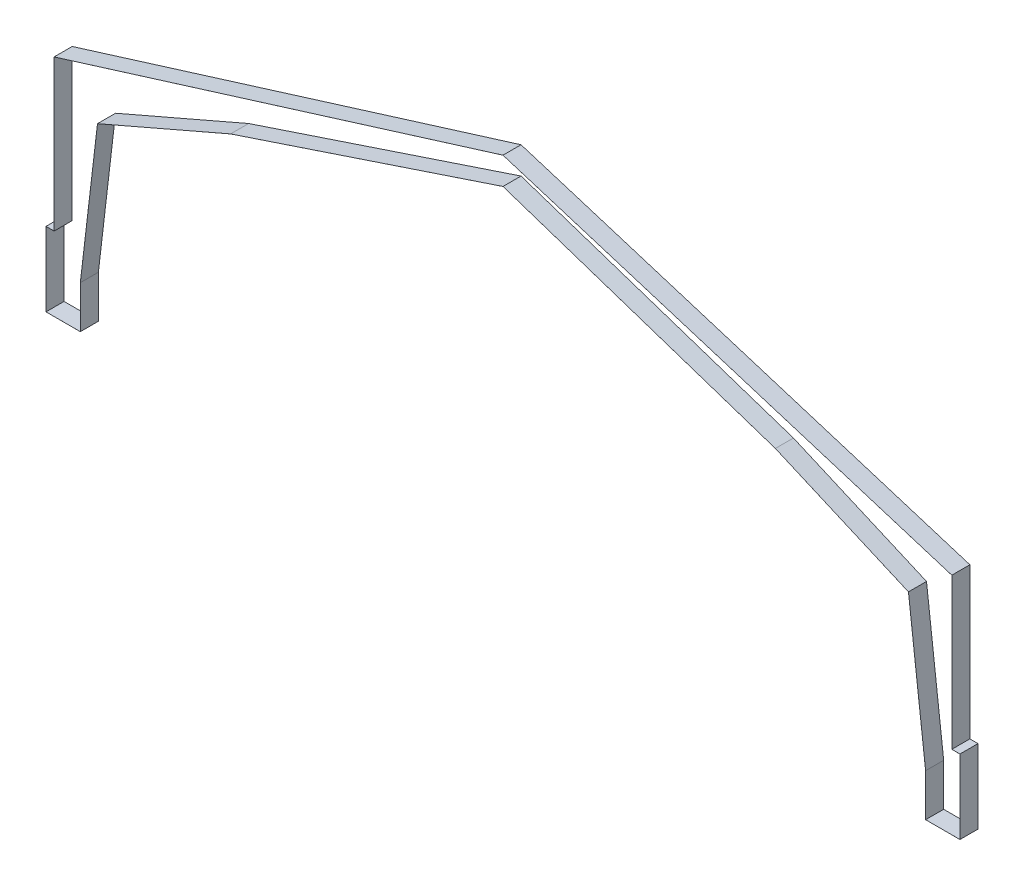
SolidWorks part; units mm, degrees
ref_plane "Alzado" through (0, 0, 0) normal (0, 0, 1) x (1, 0, 0)
ref_plane "Planta" through (0, 0, 0) normal (0, 1, 0) x (1, 0, 0)
ref_plane "Vista lateral" through (0, 0, 0) normal (1, 0, 0) x (0, 0, -1)
sketch "Croquis1" plane through (0, 0, 0) normal (0, 0, 1) x (1, 0, 0)
  line L0 (1447.8, 5308.6) -> (5191.7017, 6929.9999)
  line L1 (5191.7017, 6929.9999) -> (12852.4, 9480.804)
  line L2 (1447.8, 5308.6) -> (965.2, 1193.8)
  line L3 (12852.4, 9480.804) -> (12852.4, 12181.3588) construction
  line L11 (12852.4, 10242.804) -> (228.6, 6324.6)
  line L12 (0, 2082.8) -> (0, 0)
  line L13 (0, 0) -> (965.2, 0)
  line L14 (965.2, 1193.8) -> (965.2, 0)
  line L15 (0, 2082.8) -> (228.6, 2082.8)
  line L16 (228.6, 2082.8) -> (228.6, 6324.6)
  line L17 (25704.8, 2082.8) -> (25476.2, 2082.8)
  line L18 (25704.8, 2082.8) -> (25704.8, 0)
  line L19 (24739.6, 1193.8) -> (24739.6, 0)
  line L20 (25704.8, 0) -> (24739.6, 0)
  line L21 (24257, 5308.6) -> (24739.6, 1193.8)
  line L22 (25476.2, 2082.8) -> (25476.2, 6324.6)
  line L23 (24257, 5308.6) -> (20513.0983, 6929.9999)
  line L24 (12852.4, 10242.804) -> (25476.2, 6324.6)
  line L25 (20513.0983, 6929.9999) -> (12852.4, 9480.804)
  point P3 (0, 2780.1355)
  point P4 (0, 0)
  point P8 (0, 0)
  point P9 (327.8618, 6324.6)
  point P11 (1750.9263, 5308.6)
  dimension "D1" = 762
  dimension "D2" = 2082.8
  dimension "D3" = 5
  dimension "D4" = 4079.9188
  dimension "D5" = 5308.6
  dimension "D6" = 965.2
  dimension "D7" = 1193.8
  dimension "D8" = 4172.204
  dimension "D9" = 228.6
  dimension "D10" = 1016
  dimension "D11" = 23774.4
  dimension "D12" = 1219.2
extrude "Extruir-Lámina1" add sketch "Croquis1" along normal mid plane 508 thin thin type one direction wall 0.254
